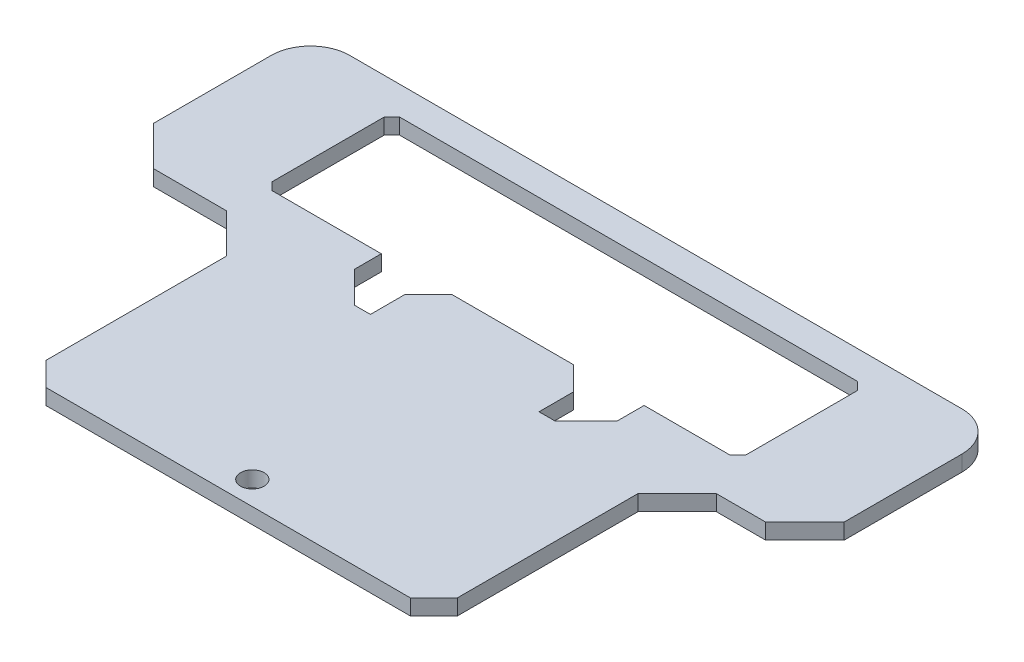
SolidWorks part; units mm, degrees
ref_plane "Front Plane" through (0, 0, 0) normal (0, 0, 1) x (1, 0, 0)
ref_plane "Top Plane" through (0, 0, 0) normal (0, 1, 0) x (1, 0, 0)
ref_plane "Right Plane" through (0, 0, 0) normal (1, 0, 0) x (0, 0, -1)
sketch "Sketch2" plane through (0, 0, 0) normal (0, 1, 0) x (1, 0, 0)
  line L1 (-35, 25) -> (35, 25)
  line L2 (-35, 25) -> (-35, -25)
  line L3 (-35, -25) -> (35, -25)
  line L4 (35, 25) -> (35, -25)
  line L5 (-35, 25) -> (35, -25) construction
  line L6 (-35, -25) -> (35, 25) construction
  point P0 (0, 0)
  dimension "D1" = 50
  dimension "D2" = 70
extrude "Boss-Extrude1" add sketch "Sketch2" along normal blind 2
sketch "Sketch3" plane through (0, 2, 0) normal (0, 1, 0) x (1, 0, 0)
  line L0 (-35, -25) -> (35, -25) construction
  line L1 (-35, 25) -> (-22, 25)
  line L2 (-35, 25) -> (-35, -25)
  line L3 (-35, -25) -> (-22, -25)
  line L4 (-22, 25) -> (-22, -25)
  line L6 (35, 25) -> (22, 25)
  line L7 (35, 25) -> (35, -25)
  line L8 (35, -25) -> (22, -25)
  line L9 (22, 25) -> (22, -25)
extrude "Cut-Extrude1" cut sketch "Sketch3" against normal through all
ref_plane "Plane1" through (22, 2, 25) normal (1, 0, 0) x (0, 0, -1)
sketch "Sketch9" plane through (0, 2, 0) normal (0, 1, 0) x (1, 0, 0)
  line L0 (-22, -25) -> (-22, 25) construction
  line L1 (-22, 25) -> (22, 25)
  line L2 (-22, 25) -> (-22, 31)
  line L3 (-22, 31) -> (22, 31)
  line L4 (22, 25) -> (22, 31)
  line L5 (-22, 10.4486) -> (-33, 10.4486)
  line L6 (-22, 10.4486) -> (-22, 31)
  line L7 (-22, 31) -> (-33, 31)
  line L8 (-33, 10.4486) -> (-33, 31)
  line L10 (22, 31) -> (33, 31)
  line L11 (22, 31) -> (22, 10.4486)
  line L12 (22, 10.4486) -> (33, 10.4486)
  line L13 (33, 31) -> (33, 10.4486)
  dimension "D1" = 6
  dimension "D2" = 11
  dimension "D3" = 11
extrude "Extrude-Thin1" add sketch "Sketch9" against normal blind 2 thin contours L3 thin type one direction wall 10
sketch "Sketch13" plane through (0, 2, 0) normal (0, 1, 0) x (1, 0, 0)
sketch "Sketch14" plane through (0, 2, 0) normal (0, 1, 0) x (1, 0, 0)
sketch "Sketch15" plane through (0, 2, 0) normal (0, 1, 0) x (1, 0, 0)
  line L1 (-30, 26.4189) -> (30, 26.4189)
  line L2 (-30, 26.4189) -> (-30, 11.4189)
  line L3 (-30, 11.4189) -> (30, 11.4189)
  line L4 (30, 26.4189) -> (30, 11.4189)
  dimension "D1" = 60
extrude "Cut-Extrude2" cut sketch "Sketch15" against normal through all
chamfer "Chamfer1" distance 1 angle 45 rebuild error yes
sketch "Sketch17" plane through (0, 2, 0) normal (0, 1, 0) x (1, 0, 0)
sketch "Sketch20" plane through (0, 2, 0) normal (0, 1, 0) x (1, 0, 0)
  line L1 (-22, 31) -> (-44, 31)
  line L2 (-22, 31) -> (-22, 6)
  line L3 (-22, 6) -> (-44, 6)
  line L4 (-44, 31) -> (-44, 6)
  line L5 (22, 31) -> (44, 31)
  line L6 (22, 31) -> (22, 6)
  line L7 (22, 6) -> (44, 6)
  line L8 (44, 31) -> (44, 6)
  dimension "D1" = 25
  dimension "D2" = 25
  dimension "D3" = 22
  dimension "D4" = 22
extrude "Boss-Extrude5" add sketch "Sketch20" against normal through all
sketch "Sketch21" plane through (0, 2, 0) normal (0, 1, 0) x (1, 0, 0)
  line L1 (-30, 27.3746) -> (30.3345, 27.3746)
  line L2 (-30, 27.3746) -> (-30, 11.1231)
  line L3 (-30, 11.1231) -> (30.3345, 11.1231)
  line L4 (30.3345, 27.3746) -> (30.3345, 11.1231)
extrude "Cut-Extrude3" cut sketch "Sketch21" against normal through all
chamfer "Chamfer5" distance 1 angle 45 4 edges at (-30, 1, -27.3746) (-30, 1, -11.1231) (30.3345, 1, -11.1231) (30.3345, 1, -27.3746)
sketch "Sketch22" plane through (0, 2, 0) normal (0, 1, 0) x (1, 0, 0)
  line L1 (-22, 6) -> (-24.7, 6)
  line L2 (-22, 6) -> (-22, -25)
  line L3 (-22, -25) -> (-24.7, -25)
  line L4 (-24.7, 6) -> (-24.7, -25)
  line L5 (22, 6) -> (27.7219, 6)
  line L6 (22, 6) -> (22, -25)
  line L7 (22, -25) -> (27.7219, -25)
  line L8 (27.7219, 6) -> (27.7219, -25)
extrude "Boss-Extrude6" add sketch "Sketch22" against normal through all
chamfer "Chamfer6" distance 5 angle 45 4 edges at (-24.7, 1, -6) (-44, 1, -6) (27.7219, 1, -6) (44, 1, -6)
fillet "Fillet2" radius 5 2 edges at (-44, 1, -31) (44, 1, -31)
chamfer "Chamfer8" distance 3 angle 45 2 edges at (27.7219, 1, 25) (-24.7, 1, 25)
sketch "Sketch23" plane through (0, 2, 0) normal (0, 1, 0) x (1, 0, 0)
  line L0 (-29, 11.1231) -> (29.3345, 11.1231) construction
  line L1 (-9.0956, 3.7335) -> (-15.0956, 3.7335)
  line L2 (-9.0956, 3.7335) -> (-9.0956, 11.1231)
  line L3 (-9.0956, 11.1231) -> (-15.0956, 11.1231)
  line L4 (-15.0956, 3.7335) -> (-15.0956, 11.1231)
  line L6 (12.3886, 3.7335) -> (18.3886, 3.7335)
  line L7 (12.3886, 3.7335) -> (12.3886, 11.1231)
  line L8 (12.3886, 11.1231) -> (18.3886, 11.1231)
  line L9 (18.3886, 3.7335) -> (18.3886, 11.1231)
  dimension "D1" = 6
  dimension "D2" = 6
extrude "Cut-Extrude4" cut sketch "Sketch23" against normal through all
sketch "Sketch24" plane through (0, 2, 0) normal (0, 1, 0) x (1, 0, 0)
  line L0 (-11.6114, -22) -> (14.7886, -22) construction
  circle A0 centre (1.5886, -22) radius 1.5
  point P2 (0.5177, -21.1154)
  point P3 (1.5886, -22)
  dimension "D1" = 3
extrude "Cut-Extrude5" cut sketch "Sketch24" against normal through all
chamfer "Chamfer11" distance 3 angle 45 2 edges at (-9.0956, 1, -11.1231) (12.3886, 1, -11.1231)
ref_plane "Plane2" through (18.3886, 0, -3.7335) normal (0, 1, 0) x (1, 0, 0)
chamfer "Chamfer12" distance 4 angle 45 2 edges at (-15.0956, 1, -3.7335) (18.3886, 1, -3.7335)
